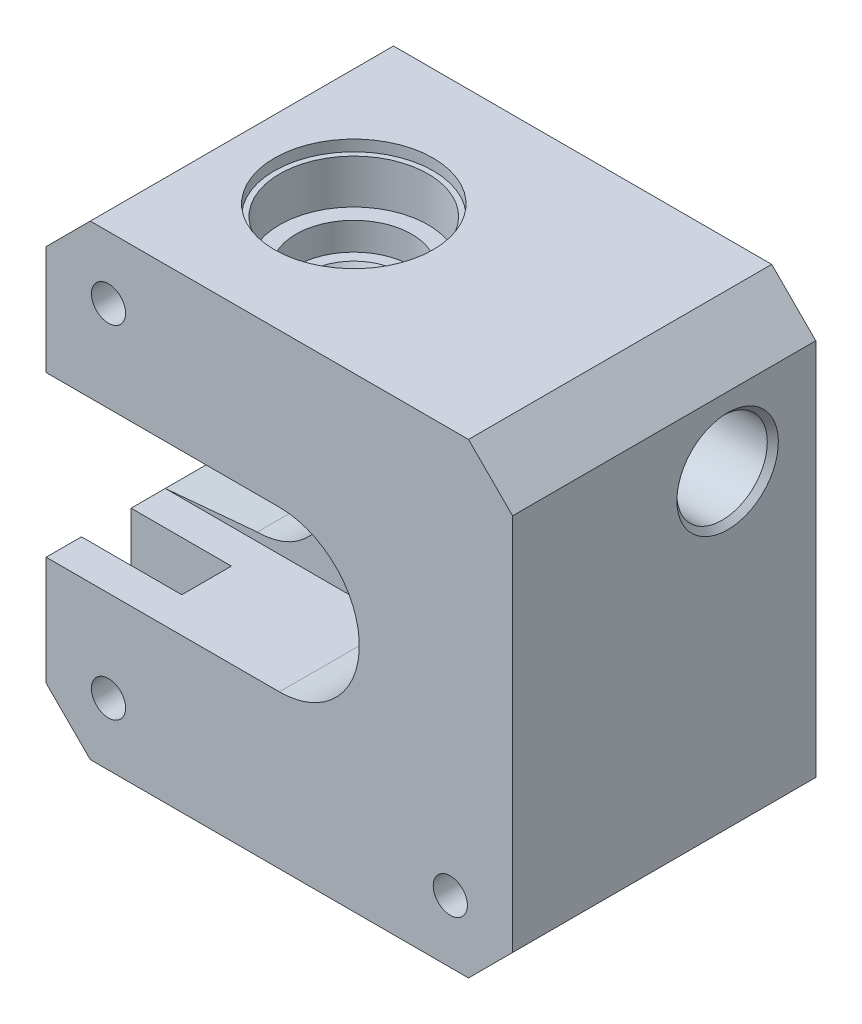
SolidWorks part; units mm, degrees
material "aluminio"
ref_plane "Alzado" through (0, 0, 0) normal (0, 0, 1) x (1, 0, 0)
ref_plane "Planta" through (0, 0, 0) normal (0, 1, 0) x (1, 0, 0)
ref_plane "Vista lateral" through (0, 0, 0) normal (1, 0, 0) x (0, 0, -1)
sketch "Croquis1" plane through (0, 0, 0) normal (0, 0, 1) x (1, 0, 0)
  line L1 (0, 0) -> (42.3, 0)
  line L2 (0, 0) -> (0, 42.3)
  line L3 (0, 42.3) -> (42.3, 42.3)
  line L4 (42.3, 0) -> (42.3, 42.3)
  dimension "D1" = 42.3
  dimension "D2" = 42.3
extrude "Saliente-Extruir1" add sketch "Croquis1" along normal blind 28
chamfer "Chaflán1" distance 4 angle 45 4 edges at (42.3, 0, 14) (0, 0, 14) (42.3, 42.3, 14) (0, 42.3, 14)
sketch "Croquis5" plane through (0, 0, 28) normal (0, 0, 1) x (1, 0, 0)
  line L0 (0, 38.3) -> (0, 4) construction
  line L1 (0, 28.4) -> (28.4, 28.4)
  line L2 (0, 28.4) -> (0, 13.9)
  line L3 (0, 13.9) -> (28.4, 13.9)
  line L4 (28.4, 28.4) -> (28.4, 13.9)
  line L5 (42.3, 21.15) -> (28.4, 21.15) construction
  line L6 (42.3, 4) -> (42.3, 38.3) construction
  dimension "D1" = 14.5
  dimension "D2" = 28.4
extrude "Cortar-Extruir4" cut sketch "Croquis5" against normal up to surface (28 mm away) up to face at (21.15, 21.15, 0)
sketch "Croquis6" plane through (0, 0, 0) normal (-1, 0, 0) x (0, 0, 1)
  line L0 (0, 28.4) -> (28, 28.4) construction
  line L1 (11.7, 28.4) -> (16.7, 28.4)
  line L2 (11.7, 28.4) -> (11.7, 13.9)
  line L3 (11.7, 13.9) -> (16.7, 13.9)
  line L4 (16.7, 28.4) -> (16.7, 13.9)
  line L6 (0, 13.9) -> (28, 13.9) construction
  line L7 (0, 13.9) -> (0, 28.4) construction
  dimension "D1" = 5
  dimension "D2" = 11.7
extrude "Saliente-Extruir2" add sketch "Croquis6" against normal up to surface (28.4 mm away) up to face at (28.4, 21.15, 14)
sketch "Croquis7" plane through (0, 0, 16.7) normal (0, 0, 1) x (1, 0, 0)
  line L0 (0, 21.15) -> (8.35, 21.15) construction
  line L1 (0, 13.9) -> (0, 28.4) construction
  line L2 (0, 27.65) -> (8.35, 27.65)
  line L3 (0, 14.65) -> (8.35, 14.65)
  line L4 (0, 13.9) -> (0, 4) construction
  line L5 (14.7726, 22.15) -> (14.8286, 22.15)
  line L6 (21.15, 21.15) -> (42.3, 21.15) construction
  line L7 (42.3, 4) -> (42.3, 38.3) construction
  line L11 (14.7726, 20.15) -> (14.8286, 20.15)
  arc A0 (14.8286, 20.15) -> (14.8286, 22.15) centre (21.15, 21.15) ccw
  arc A1 (0, 27.65) -> (0, 14.65) centre (0, 21.15) ccw
  arc A2 (8.35, 14.65) -> (14.7726, 20.15) centre (8.35, 21.15) ccw
  arc A3 (14.7726, 22.15) -> (8.35, 27.65) centre (8.35, 21.15) ccw
  dimension "D1" = 6.5
  dimension "D2" = 12.8
  dimension "D6" = 6.5
  dimension "D3" = 12.8
  dimension "D4" = 21.15
  dimension "D5" = 2
extrude "Cortar-Extruir5" cut sketch "Croquis7" against normal up to next
sketch "Croquis3" plane through (0, 42.3, 0) normal (0, 1, 0) x (1, 0, 0)
  line L0 (4, -14.2) -> (14.6, -14.2) construction
  line L2 (0, -28) -> (0, 0) construction
  line L3 (38.3, 0) -> (4, 0) construction
  circle A0 centre (14.6, -14.2) radius 1.9
  dimension "D1" = 3.8
  dimension "D2" = 14.6
  dimension "D3" = 14.2
extrude "Cortar-Extruir2" cut sketch "Croquis3" against normal through all
sketch "Croquis8" plane through (0, 0, 11.7) normal (0, 0, -1) x (-1, 0, 0)
  line L0 (-8.35, 14.65) -> (0, 13.9)
  line L1 (0, 13.9) -> (0, 14.65)
  line L2 (0, 14.65) -> (-8.35, 14.65)
  line L3 (0, 28.4) -> (-8.35, 27.65)
  line L4 (-8.35, 27.65) -> (0, 27.65)
  line L5 (0, 27.65) -> (0, 28.4)
extrude "Cortar-Extruir6" cut sketch "Croquis8" against normal blind 20
sketch "Croquis9" plane through (0, 0, 0) normal (0, 0, -1) x (-1, 0, 0)
  line L0 (-36.65, 36.65) -> (-5.65, 36.65) construction
  line L1 (-5.65, 36.65) -> (-5.65, 5.65) construction
  line L2 (-5.65, 5.65) -> (-36.65, 5.65) construction
  line L3 (-36.65, 5.65) -> (-36.65, 36.65) construction
  line L4 (-21.15, 36.65) -> (-21.15, 42.3) construction
  line L5 (-38.3, 42.3) -> (-4, 42.3) construction
  line L6 (-42.3, 21.15) -> (-36.65, 21.15) construction
  line L7 (-42.3, 4) -> (-42.3, 38.3) construction
  circle A0 centre (-36.65, 36.65) radius 1.55 construction
  circle A1 centre (-5.65, 36.65) radius 1.55
  circle A2 centre (-5.65, 5.65) radius 1.55
  circle A3 centre (-36.65, 5.65) radius 1.55
  dimension "D2" = 3.1
  dimension "D1" = 31
extrude "Cortar-Extruir7" cut sketch "Croquis9" against normal up to surface (28 mm away) up to face at (18.8333, 21.15, 28)
sketch "Croquis10" plane through (0, 42.3, 0) normal (0, 1, 0) x (1, 0, 0)
  circle A0 centre (14.6, -14.2) radius 6.725
  dimension "D1" = 13.45
extrude "Cortar-Extruir8" cut sketch "Croquis10" against normal blind 5
sketch "Croquis11" plane through (0, 37.3, 0) normal (0, 1, 0) x (1, 0, 0)
  circle A0 centre (14.6, -14.2) radius 5.25
  dimension "D1" = 10.5
extrude "Cortar-Extruir9" cut sketch "Croquis11" against normal blind 2.5
sketch "Croquis12" plane through (0, 34.8, 0) normal (0, 1, 0) x (1, 0, 0)
  circle A0 centre (14.6, -14.2) radius 3.25
  dimension "D1" = 6.5
extrude "Cortar-Extruir10" cut sketch "Croquis12" against normal blind 6
sketch "Croquis15" plane through (0, 42.3, 0) normal (0, 1, 0) x (1, 0, 0)
  circle A0 centre (14.6, -14.2) radius 7.2
  dimension "D1" = 14.4
extrude "Cortar-Extruir13" cut sketch "Croquis15" against normal blind 1
chamfer "Chaflán2" distance 1 angle 60 1 edges at (14.6, 34.8, 17.45) first distance on face at (14.6, 34.8, 17.45)
ref_plane "Plano1" through (0, 21.15, 0) normal (0, 1, 0) x (1, 0, 0)
mirror "Simetría1" about plane through (0, 21.15, 0) normal (0, 1, 0) of "Cortar-Extruir13", "Cortar-Extruir8", "Cortar-Extruir9", "Cortar-Extruir10"
chamfer "Chaflán4" distance 1 angle 60 1 edges at (14.6, 7.5, 17.45) first distance on face at (14.6, 7.5, 17.45)
chamfer "Chaflán5" distance 0.7 angle 60 1 edges at (14.6, 13.5, 12.3) first distance on face at (14.6, 13.5, 17.45)
chamfer "Chaflán6" [suppressed] distance 0.5 angle 60
ref_plane "Plano2" through (0, 0, 14) normal (0, 0, 1) x (1, 0, 0)
sketch "Croquis18" plane through (0, 42.3, 0) normal (0, 1, 0) x (1, 0, 0)
  line L0 (12, -24.5) -> (24, -24.5) construction
  line L1 (12, -22.5) -> (24, -22.5) construction
  line L2 (12, -26.5) -> (24, -26.5) construction
  line L3 (38.3, -28) -> (4, -28) construction
  line L4 (4, -14) -> (38.3, -14) construction
  line L5 (0, -28) -> (0, 0) construction
  line L6 (4, 0) -> (4, -28) construction
  line L7 (38.3, -28) -> (38.3, 0) construction
  line L8 (12, -3.5) -> (24, -3.5) construction
  line L9 (12, -5.5) -> (24, -5.5)
  line L10 (12, -1.5) -> (24, -1.5)
  arc A0 (12, -22.5) -> (12, -26.5) centre (12, -24.5) ccw construction
  arc A1 (24, -26.5) -> (24, -22.5) centre (24, -24.5) ccw construction
  arc A2 (12, -5.5) -> (12, -1.5) centre (12, -3.5) cw
  arc A3 (24, -1.5) -> (24, -5.5) centre (24, -3.5) cw
  point P2 (18, -24.5)
  point P19 (18, -3.5)
  dimension "D1" = 2
  dimension "D2" = 12
  dimension "D3" = 1.5
  dimension "D4" = 12
extrude "Cortar-Extruir17" cut sketch "Croquis18" against normal up to surface (13.9 mm away) from surface at -28.4 up to face at (14.6, 0, 21.4) starting at face at (14.2, 13.9, 5.85)
sketch "Croquis21" plane through (0, 0, 16.7) normal (0, 0, 1) x (1, 0, 0)
  line L1 (14.5014, 23.25) -> (15.1043, 23.25)
  line L2 (14.5014, 23.25) -> (14.5014, 19.05)
  line L3 (14.5014, 19.05) -> (15.1043, 19.05)
  line L4 (15.1043, 23.25) -> (15.1043, 19.05)
  arc A0 (8.35, 14.65) -> (14.7726, 20.15) centre (8.35, 21.15) ccw construction
  circle A1 centre (21.15, 21.15) radius 6.4 construction
  dimension "D1" = 4.2
  dimension "D2" = 0.6029
extrude "Cortar-Extruir19" cut sketch "Croquis21" against normal through all
sketch "Croquis22" plane through (0, 0, 0) normal (-1, 0, 0) x (0, 0, 1)
  line L2 (8, 32.3) -> (8, 31.8) construction
  line L3 (9.55, 32.3) -> (9.55, 31.8) construction
  line L4 (6.45, 32.3) -> (6.45, 31.8) construction
  line L5 (0, 38.3) -> (0, 28.4) construction
  line L6 (0, 42.3) -> (28, 42.3) construction
  arc A0 (9.55, 32.3) -> (6.45, 32.3) centre (8, 32.3) ccw construction
  arc A1 (6.45, 31.8) -> (9.55, 31.8) centre (8, 31.8) ccw construction
  circle A2 centre (8, 32.05) radius 2.5
  point P2 (8, 32.05)
  dimension "D1" = 1.55
  dimension "D5" = 5
  dimension "D2" = 0.5
  dimension "D3" = 8
  dimension "D4" = 10
extrude "Cortar-Extruir20" cut sketch "Croquis22" against normal through all
fillet "Redondeo1" radius 0.4 8 edges at (14.5014, 19.05, 12.0013) (15.1043, 19.05, 12.0341) (15.1043, 19.05, 16.3659) (14.5014, 19.05, 16.3987) (15.1043, 23.25, 16.3659) (15.1043, 23.25, 12.0341) (14.5014, 23.25, 12.0013) (14.5014, 23.25, 16.3987)
sketch "Croquis25" plane through (0, 42.3, 0) normal (0, 1, 0) x (1, 0, 0)
  line L0 (42.3, 0) -> (42.3, -28) construction
  line L1 (0, -28) -> (42.3, -28)
  line L2 (0, -28) -> (0, -27.5)
  line L3 (0, -27.5) -> (42.3, -27.5)
  line L4 (42.3, -28) -> (42.3, -27.5)
  dimension "D1" = 0.5
extrude "Cortar-Extruir23" cut sketch "Croquis25" against normal through all
sketch "Croquis34" plane through (0, 0, 0) normal (-1, 0, 0) x (0, 0, 1)
  line L0 (27.5, 0) -> (0, 0) construction
  line L1 (0, 13.9) -> (1.8, 13.9)
  line L2 (0, 13.9) -> (0, 0)
  line L3 (0, 0) -> (1.8, 0)
  line L4 (1.8, 13.9) -> (1.8, 0)
  line L5 (16.7, 13.9) -> (27.5, 13.9) construction
  line L6 (19.8, 13.9) -> (24.3, 13.9)
  line L7 (19.8, 13.9) -> (19.8, 0)
  line L8 (19.8, 0) -> (24.3, 0)
  line L9 (24.3, 13.9) -> (24.3, 0)
  dimension "D1" = 1.8
  dimension "D2" = 19.8
  dimension "D3" = 4.5
extrude "Cortar-Extruir28" cut sketch "Croquis34" against normal blind 9.1
fillet "Redondeo6" radius 7.25 4 edges at (28.4, 28.4, 5.85) (28.4, 13.9, 5.85) (28.4, 13.9, 22.1) (28.4, 28.4, 22.1)
sketch "Croquis35" plane through (0, 0, 0) normal (-1, 0, 0) x (0, 0, 1)
  line L0 (0, 28.4) -> (0, 21.15) construction
  line L2 (24.7, 27.4) -> (24.7, 29.15)
  line L3 (0, 27.4) -> (0, 42.3)
  line L4 (0, 42.3) -> (12.7, 42.3)
  line L5 (0, 42.3) -> (27.5, 42.3) construction
  line L6 (12.7, 42.3) -> (12.7, 37.65)
  line L7 (12.7, 37.65) -> (16.2, 37.65)
  line L8 (27.5, 28.4) -> (27.5, 38.3) construction
  line L9 (0, 27.4) -> (24.7, 27.4)
  line L10 (0, 28.4) -> (11.7, 28.4) construction
  arc A0 (16.2, 37.65) -> (24.7, 29.15) centre (16.2, 29.15) cw
  dimension "D1" = 8.5
  dimension "D2" = 2.8
  dimension "D3" = 4.65
  dimension "D4" = 12.7
  dimension "D5" = 1
extrude "Cortar-Extruir29" cut sketch "Croquis35" against normal blind 3.9
fillet "Redondeo7" radius 2 1 edges at (1.95, 37.65, 12.7)
sketch "Croquis24" plane through (42.3, 0, 0) normal (1, 0, 0) x (0, 0, -1)
  circle A0 centre (-8, 32.05) radius 4.1
  dimension "D1" = 8.2
extrude "Cortar-Extruir22" cut sketch "Croquis24" against normal blind 17
chamfer "Chaflán7" distance 0.5 angle 45 1 edges at (42.3, 36.15, 8)
sketch "Croquis36" plane through (0, 0, 0) normal (0, 0, -1) x (-1, 0, 0)
  line L0 (-35.2995, 31.0495) -> (-35.2995, 11.2505)
  line L1 (-31.0495, 35.2995) -> (-11.2505, 35.2995)
  line L2 (-24, 0) -> (-24, 14.4837) construction
  line L3 (-26.7995, 11.2505) -> (-26.7995, 26.7995)
  line L4 (-26.7995, 26.7995) -> (-11.2505, 26.7995)
  line L5 (-7.0005, 31.0495) -> (-7.0005, 28.4)
  line L6 (-21.15, 28.4) -> (-3.9, 28.4) construction
  line L10 (-3.9, 28.4) -> (-3.9, 42.2)
  line L11 (-3.9, 42.2) -> (-4, 42.3)
  line L12 (-4, 42.3) -> (-38.3, 42.3)
  line L13 (-38.3, 42.3) -> (-42.3, 38.3)
  line L14 (-42.3, 38.3) -> (-42.3, 4)
  line L15 (-42.3, 4) -> (-38.3, 0)
  line L16 (-38.3, 0) -> (-9.1, 0)
  line L17 (-9.1, 0) -> (-9.1, 13.9)
  line L18 (-9.1, 13.9) -> (-21.15, 13.9)
  line L19 (-21.15, 28.4) -> (-3.9, 28.4)
  line L20 (-3.9, 28.4) -> (-3.9, 42.2)
  line L21 (-3.9, 42.2) -> (-4, 42.3)
  line L22 (-4, 42.3) -> (-38.3, 42.3)
  line L23 (-38.3, 42.3) -> (-42.3, 38.3)
  line L24 (-42.3, 38.3) -> (-42.3, 4)
  line L25 (-42.3, 4) -> (-38.3, 0)
  line L26 (-38.3, 0) -> (-9.1, 0)
  line L27 (-9.1, 0) -> (-9.1, 13.9)
  line L28 (-9.1, 13.9) -> (-24, 13.9)
  circle A0 centre (-31.0495, 11.2505) radius 2.75 construction
  circle A1 centre (-11.2505, 31.0495) radius 2.75 construction
  arc A2 (-28.4, 21.15) -> (-21.15, 13.9) centre (-21.15, 21.15) ccw
  arc A3 (-21.15, 28.4) -> (-28.4, 21.15) centre (-21.15, 21.15) ccw
  arc A4 (-28.4, 21.15) -> (-21.15, 13.9) centre (-21.15, 21.15) ccw
  arc A5 (-21.15, 28.4) -> (-28.4, 21.15) centre (-21.15, 21.15) ccw
  circle A6 centre (-31.0495, 31.0495) radius 2.75 construction
  circle A7 centre (-31.0495, 11.2505) radius 2.75 construction
  circle A8 centre (-11.2505, 31.0495) radius 2.75 construction
  circle A9 centre (-31.0495, 31.0495) radius 2.75 construction
  circle A10 centre (-11.2505, 31.0495) radius 4.25
  circle A11 centre (-31.0495, 31.0495) radius 4.25
  circle A12 centre (-31.0495, 11.2505) radius 4.25
  dimension "D2" = 8.5
  dimension "D1" = 0
extrude "Cortar-Extruir30" cut sketch "Croquis36" against normal blind 3.1
fillet "Redondeo10" radius 0.5 1 edges at (26.7995, 16.6062, 1.55) type face fillet first side face at (24.7244, 15.8778, 4.3388) second side face at (26.7995, 13.9284, 1.55)
sketch "Croquis37" plane through (0, 0, 0) normal (0, 0, -1) x (-1, 0, 0)
  line L0 (-7.0005, 31.0495) -> (-7.0005, 28.4) construction
  line L1 (-26.7995, 11.2505) -> (-26.7995, 15.3582) construction
  line L2 (-35.2995, 31.0495) -> (-35.2995, 11.2505) construction
  line L3 (-31.0495, 35.2995) -> (-11.2505, 35.2995) construction
  line L4 (-7.0005, 31.0495) -> (-7.0005, 28.4)
  line L5 (-26.7995, 11.2505) -> (-26.7995, 15.3582)
  line L6 (-35.2995, 31.0495) -> (-35.2995, 11.2505) construction
  line L7 (-31.0495, 35.2995) -> (-11.2505, 35.2995) construction
  line L8 (-31.0495, 7.0005) -> (-34.0495, 7.0005)
  line L9 (-37.2995, 31.0495) -> (-37.2995, 10.2505)
  line L11 (-31.0495, 37.2995) -> (-10.2505, 37.2995)
  line L12 (-37.2995, 31.0495) -> (-37.2995, 11.2505) construction
  line L13 (-24.7995, 11.2505) -> (-24.7995, 15.3582) construction
  line L15 (-7.0005, 31.0495) -> (-7.0005, 34.0495)
  line L16 (-26.7995, 15.3582) -> (-26.7995, 28.4)
  line L17 (-26.7995, 28.4) -> (-7.0005, 28.4)
  line L18 (-5.0005, 31.0495) -> (-5.0005, 28.4) construction
  line L20 (-31.0495, 37.2995) -> (-11.2505, 37.2995) construction
  arc A0 (-7.0005, 31.0495) -> (-11.2505, 35.2995) centre (-11.2505, 31.0495) ccw construction
  arc A1 (-35.2995, 11.2505) -> (-26.7995, 11.2505) centre (-31.0495, 11.2505) ccw construction
  arc A2 (-31.0495, 35.2995) -> (-35.2995, 31.0495) centre (-31.0495, 31.0495) ccw construction
  arc A3 (-7.0005, 31.0495) -> (-11.2505, 35.2995) centre (-11.2505, 31.0495) ccw construction
  arc A4 (-31.0495, 7.0005) -> (-26.7995, 11.2505) centre (-31.0495, 11.2505) ccw
  arc A5 (-31.0495, 35.2995) -> (-35.2995, 31.0495) centre (-31.0495, 31.0495) ccw construction
  arc A6 (-37.2995, 10.2505) -> (-34.0495, 7.0005) centre (-34.0495, 10.2505) ccw
  arc A7 (-31.0495, 37.2995) -> (-37.2995, 31.0495) centre (-31.0495, 31.0495) ccw
  arc A9 (-10.2505, 37.2995) -> (-7.0005, 34.0495) centre (-10.2505, 34.0495) cw
  arc A10 (-35.2995, 11.2505) -> (-26.7995, 11.2505) centre (-31.0495, 11.2505) ccw construction
  arc A14 (-37.2995, 11.2505) -> (-24.7995, 11.2505) centre (-31.0495, 11.2505) ccw construction
  arc A15 (-5.0005, 31.0495) -> (-11.2505, 37.2995) centre (-11.2505, 31.0495) ccw construction
  dimension "D2" = 3.25
  dimension "D3" = 3.25
  dimension "D1" = 2
extrude "Cortar-Extruir32" [suppressed] cut sketch "Croquis37" against normal blind 3.1
sketch "Croquis38" plane through (0, 0, 11.7) normal (0, 0, -1) x (-1, 0, 0)
  line L0 (-9.1, 13.9) -> (-21.15, 13.9) construction
  line L1 (-21.15, 28.4) -> (-3.9, 28.4) construction
  line L2 (-9.1, 13.9) -> (-21.15, 13.9) construction
  line L3 (-21.15, 28.4) -> (-3.9, 28.4) construction
  line L4 (-28.4, 21.15) -> (-21.15, 21.15) construction
  line L5 (-22, 27.55) -> (-21.15, 27.55)
  line L6 (-21.15, 14.75) -> (-22, 14.75)
  arc A0 (-15.1982, 23.5029) -> (-15.1982, 18.7971) centre (-21.15, 21.15) ccw construction
  arc A1 (-15.1982, 23.5029) -> (-15.1982, 18.7971) centre (-21.15, 21.15) ccw construction
  arc A2 (-21.15, 28.4) -> (-28.4, 21.15) centre (-21.15, 21.15) ccw construction
  arc A3 (-28.4, 21.15) -> (-21.15, 13.9) centre (-21.15, 21.15) ccw construction
  arc A4 (-21.15, 28.4) -> (-28.4, 21.15) centre (-21.15, 21.15) ccw construction
  arc A5 (-28.4, 21.15) -> (-21.15, 13.9) centre (-21.15, 21.15) ccw construction
  arc A6 (-21.15, 14.75) -> (-21.15, 27.55) centre (-21.15, 21.15) ccw
  arc A7 (-22, 27.55) -> (-22, 14.75) centre (-22, 21.15) ccw
  point P10 (-28.4, 21.15)
  point P17 (-28.4, 21.15)
  dimension "D1" = 6.4
extrude "Cortar-Extruir35" cut sketch "Croquis38" against normal through all both and the other way through all
